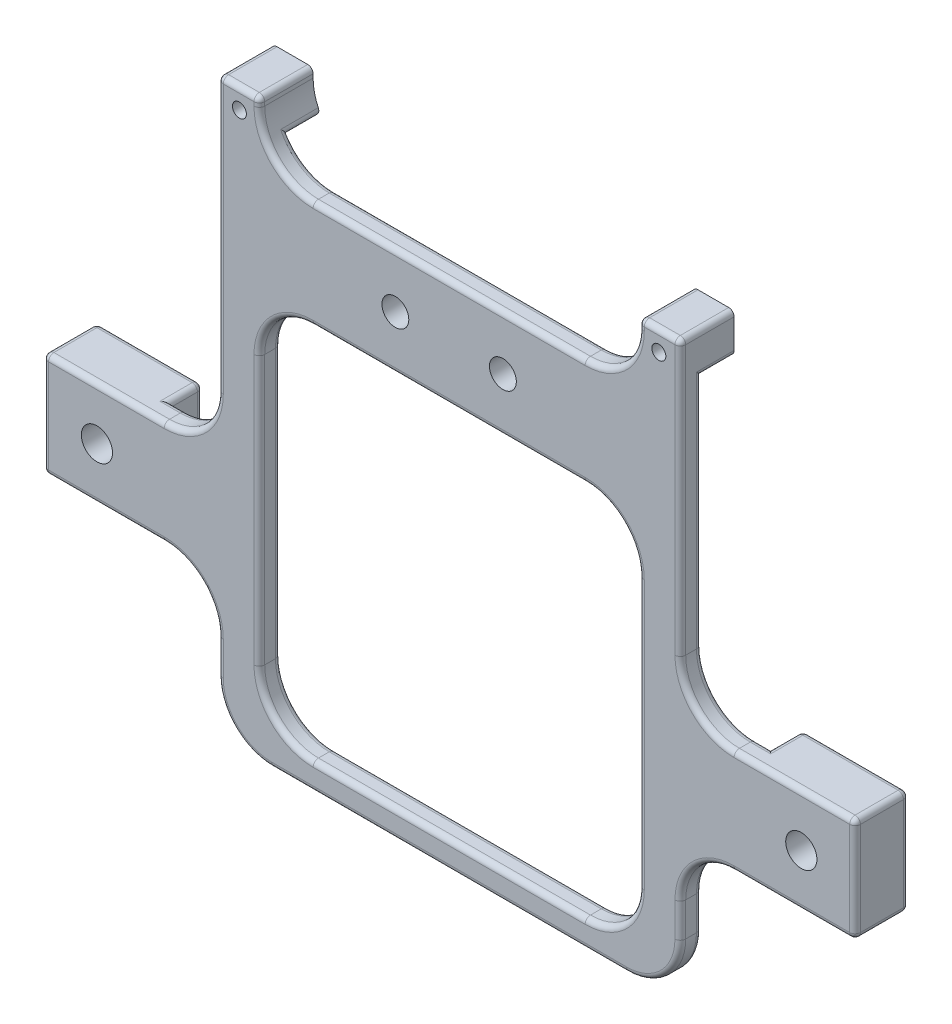
SolidWorks part; units mm, degrees
ref_plane "Plan de face" through (0, 0, 0) normal (0, 0, 1) x (1, 0, 0)
ref_plane "Plan de dessus" through (0, 0, 0) normal (0, 1, 0) x (1, 0, 0)
ref_plane "Plan de droite" through (0, 0, 0) normal (1, 0, 0) x (0, 0, -1)
sketch "Esquisse1" plane through (0, 0, 26) normal (0, 0, 1) x (1, 0, 0)
  line L0 (19.7071, 95.7071) -> (19.7071, 76.2929)
  line L1 (19.7071, 95.7071) -> (0, 95.7071)
  line L2 (19.7071, 76.2929) -> (0, 76.2929)
  line L3 (0, 95.7071) -> (0, 76.2929)
  line L5 (131.2929, 95.7071) -> (131.2929, 76.2929)
  line L6 (131.2929, 95.7071) -> (151, 95.7071)
  line L7 (131.2929, 76.2929) -> (151, 76.2929)
  line L8 (151, 95.7071) -> (151, 76.2929)
  line L9 (110.7929, 156.7071) -> (110.7929, 149.2929)
  line L10 (110.7929, 156.7071) -> (118.5, 156.7071)
  line L11 (110.7929, 149.2929) -> (118.5, 149.2929)
  line L12 (118.5, 156.7071) -> (118.5, 149.2929)
  line L13 (40.2071, 156.7071) -> (40.2071, 149.2929)
  line L14 (40.2071, 156.7071) -> (32.5, 156.7071)
  line L15 (40.2071, 149.2929) -> (32.5, 149.2929)
  line L16 (32.5, 156.7071) -> (32.5, 149.2929)
  line L17 (32.5, 156) -> (32.5, 150) construction
  line L18 (118.5, 150) -> (118.5, 156) construction
  line L19 (151, 147) -> (151, 78) construction
  line L20 (0, 78) -> (0, 147) construction
  arc A0 (20, 95) -> (19, 96) centre (19, 95) ccw construction
  arc A1 (19, 76) -> (20, 77) centre (19, 77) ccw construction
  arc A2 (132, 96) -> (131, 95) centre (132, 95) ccw construction
  arc A3 (131, 77) -> (132, 76) centre (132, 77) ccw construction
  arc A4 (111.5, 157) -> (110.5, 156) centre (111.5, 156) ccw construction
  arc A5 (110.5, 150) -> (111.5, 149) centre (111.5, 150) ccw construction
  arc A6 (40.5, 156) -> (39.5, 157) centre (39.5, 156) ccw construction
  arc A7 (39.5, 149) -> (40.5, 150) centre (39.5, 150) ccw construction
  circle A8 centre (141, 86) radius 2.9
  circle A9 centre (10, 86) radius 2.9
  circle A10 centre (36.5, 153) radius 1.3
  circle A11 centre (114.5, 153) radius 1.3
  circle A12 centre (114.5, 153) radius 1.3 construction
  circle A13 centre (36.5, 153) radius 1.3 construction
  circle A14 centre (10, 86) radius 2.9 construction
  circle A15 centre (141, 86) radius 2.9 construction
extrude "Boss.-Extru.1" add sketch "Esquisse1" along normal blind 6 contours L0 L1 L3 L2 | L5 L6 L8 L7 | L9 L10 L12 L11 | L13 L14 L16 L15 | A10 | A11 | A8 | A9
sketch "Esquisse2" plane through (0, 0, 32) normal (0, 0, 1) x (1, 0, 0)
  line L0 (32.5, 156.7071) -> (32.5, 95.7071)
  line L1 (32.5, 156.7071) -> (40.2071, 156.7071)
  line L2 (32.5, 95.7071) -> (40.2071, 95.7071)
  line L3 (40.2071, 156.7071) -> (40.2071, 95.7071)
  line L4 (110.7929, 156.7071) -> (118.5, 156.7071)
  line L5 (110.7929, 156.7071) -> (110.7929, 95.7071)
  line L6 (118.5, 156.7071) -> (118.5, 95.7071)
  line L7 (110.7929, 95.7071) -> (118.5, 95.7071)
  line L8 (151, 95.7071) -> (110.7929, 95.7071)
  line L9 (151, 95.7071) -> (151, 76.2929)
  line L10 (110.7929, 95.7071) -> (110.7929, 76.2929)
  line L11 (151, 76.2929) -> (110.7929, 76.2929)
  line L12 (110.7929, 95.7071) -> (110.7929, 50)
  line L13 (110.7929, 95.7071) -> (118.5, 95.7071)
  line L14 (110.7929, 50) -> (118.5, 50)
  line L15 (118.5, 95.7071) -> (118.5, 50)
  line L16 (118.5, 50) -> (32.5, 50)
  line L17 (118.5, 50) -> (118.5, 55)
  line L18 (32.5, 50) -> (32.5, 55)
  line L19 (118.5, 55) -> (32.5, 55)
  line L20 (0, 95.7071) -> (40.2071, 95.7071)
  line L21 (0, 95.7071) -> (0, 76.2929)
  line L22 (40.2071, 95.7071) -> (40.2071, 76.2929)
  line L23 (0, 76.2929) -> (40.2071, 76.2929)
  line L24 (40.2071, 95.7071) -> (32.5, 95.7071)
  line L25 (40.2071, 95.7071) -> (40.2071, 55)
  line L26 (32.5, 95.7071) -> (32.5, 55)
  line L27 (40.2071, 55) -> (32.5, 55)
  line L28 (32.5, 145) -> (118.5, 145)
  line L29 (32.5, 145) -> (32.5, 125)
  line L30 (118.5, 145) -> (118.5, 125)
  line L31 (32.5, 125) -> (118.5, 125)
  line L32 (100.5, 145) -> (50.5, 145) construction
  line L34 (43, 50) -> (108, 50) construction
  arc A0 (111.5, 157) -> (110.5, 156) centre (111.5, 156) ccw construction
  arc A1 (40.5, 156) -> (39.5, 157) centre (39.5, 156) ccw construction
  circle A2 centre (10, 86) radius 2.9
  circle A3 centre (141, 86) radius 2.9
  circle A4 centre (114.5, 153) radius 1.3
  circle A5 centre (36.5, 153) radius 1.3
  circle A6 centre (36.5, 153) radius 1.3 construction
  circle A7 centre (114.5, 153) radius 1.3 construction
  circle A8 centre (141, 86) radius 2.9 construction
  circle A9 centre (10, 86) radius 2.9 construction
  point P44 (151, 76.2929)
  point P61 (151, 76)
  point P62 (151, 76)
  line M37 (0, 76.2929) -> (19.7071, 76.2929)
  line M38 (19.7071, 76.2929) -> (19.7071, 95.7071)
  line M39 (19.7071, 95.7071) -> (0, 95.7071)
  line M40 (0, 95.7071) -> (0, 76.2929)
  circle M41 centre (10, 86) radius 2.9
  dimension "D1" = 5
  dimension "D2" = 20
extrude "Boss.-Extru.2" add sketch "Esquisse2" along normal blind 4 contours L23 L26 L19 L25 | L2 L26 L23 L22 | L26 L20 L23 M38 | M40 M37 M38 M39 M41 | L31 L0 L2 L3 | L0 L31 L3 L28 | L3 L31 L5 L28 | L0 L28 L3 L1 A5 | L12 L19 L18 L16 | L15 L19 L12 L14 | L19 L15 L11 L12 | L15 L7 L10 L11 | L8 L15 L11 L9 A3 | L31 L5 L7 L6 | L5 L31 L6 L28 | L5 L28 L6 L4 A4 region at (36.3444, 150.7194, 32) region at (36.3536, 135, 32) region at (36.3536, 110.3536, 32) region at (75.5, 135, 32) region at (26.1036, 86, 32) region at (36.3536, 86, 32) region at (114.6464, 135, 32) region at (114.6556, 150.7194, 32) region at (19.4305, 86, 32) region at (36.3536, 65.6464, 32) region at (114.6464, 110.3536, 32) region at (71.6464, 52.5, 32) region at (114.6464, 86, 32) region at (134.4769, 86, 32) region at (114.6464, 65.6464, 32) region at (114.6464, 52.5, 32)
fillet "Congé1" radius 10 10 edges at (40.2071, 145, 34) (110.7929, 145, 34) (118.5, 76.2929, 34) (118.5, 95.7071, 34) (110.7929, 125, 34) (40.2071, 125, 34) (40.2071, 55, 34) (110.7929, 55, 34) (32.5, 95.7071, 34) (32.5, 76.2929, 34)
fillet "Congé2" radius 10 2 edges at (32.5, 50, 34) (118.5, 50, 34)
fillet "Congé3" radius 1 80 edges at (129.8964, 76.2929, 32) (32.5, 63.1464, 32) (35.4289, 52.9289, 32) (75.5, 50, 32) (115.5711, 52.9289, 32) (118.5, 63.1464, 32) (105.4259, 146.138, 32) (75.5, 145, 32) (110.7929, 155.8536, 36) (107.864, 147.9289, 36) (75.5, 145, 36) (40.2071, 155.8536, 36) (75.5, 125, 32) (107.864, 122.0711, 32) (110.7929, 90, 32) (107.864, 57.9289, 32) (75.5, 55, 32) (43.136, 57.9289, 32) (40.2071, 90, 32) (43.136, 57.9289, 36) (75.5, 55, 36) (107.864, 57.9289, 36) (107.864, 122.0711, 36) (75.5, 125, 36) (118.5, 127.5, 32) (129.8964, 95.7071, 32) (139.75, 95.7071, 36) (118.5, 131.2071, 36) (32.5, 63.1464, 36) (139.75, 76.2929, 36) (121.4289, 73.364, 36) (118.5, 63.1464, 36) (115.5711, 52.9289, 36) (75.5, 50, 36) (0, 86, 26) (0, 76.2929, 31) (0, 86, 36) (0, 95.7071, 31) (11.25, 95.7071, 36) (121.4289, 73.364, 32) (151, 95.7071, 31) (141.1464, 95.7071, 26) (151, 86, 26) (151, 86, 36) (45.5741, 146.138, 32) (43.136, 147.9289, 36) (43.136, 122.0711, 32) (43.136, 122.0711, 36) (121.4289, 98.636, 32) (121.4289, 98.636, 36) (35.4289, 52.9289, 36) (11.25, 76.2929, 36) (32.5, 131.2071, 36) (29.5711, 98.636, 36) (21.1036, 76.2929, 32) (29.5711, 73.364, 32) (29.5711, 73.364, 36) (21.1036, 95.7071, 32) (32.5, 127.5, 32) (19.7071, 76.2929, 29) (19.7071, 86, 26) (131.2929, 95.7071, 29) (36.3536, 156.7071, 36) (114.6464, 156.7071, 36) (109.0044, 149.2929, 29) (32.5, 149.2929, 29) (32.5, 156.7071, 31) (40.2071, 156.7071, 31) (41.9956, 149.2929, 29) (110.7929, 156.7071, 31) (118.5, 149.2929, 29) (118.5, 156.7071, 31) (19.7071, 95.7071, 29) (9.8536, 95.7071, 26) (29.5711, 98.636, 32) (131.2929, 86, 26) (151, 76.2929, 31) (131.2929, 76.2929, 29) (141.1464, 76.2929, 26) (9.8536, 76.2929, 26)
sketch "Esquisse5" plane through (0, 0, 36) normal (0, 0, 1) x (1, 0, 0)
  line L0 (117.5, 105.7071) -> (117.5, 155.7071) construction
  line L1 (33.5, 155.7071) -> (33.5, 105.7071) construction
  line L2 (100.7929, 144) -> (50.2071, 144) construction
  circle A0 centre (65.5, 135) radius 2.5
  circle A1 centre (85.5, 135) radius 2.5
  dimension "D5" = 5
  dimension "D6" = 5
  dimension "D1" = 20
  dimension "D2" = 32
  dimension "D3" = 32
  dimension "D4" = 9
extrude "Enlèv. mat.-Extru.1" cut sketch "Esquisse5" against normal through all
